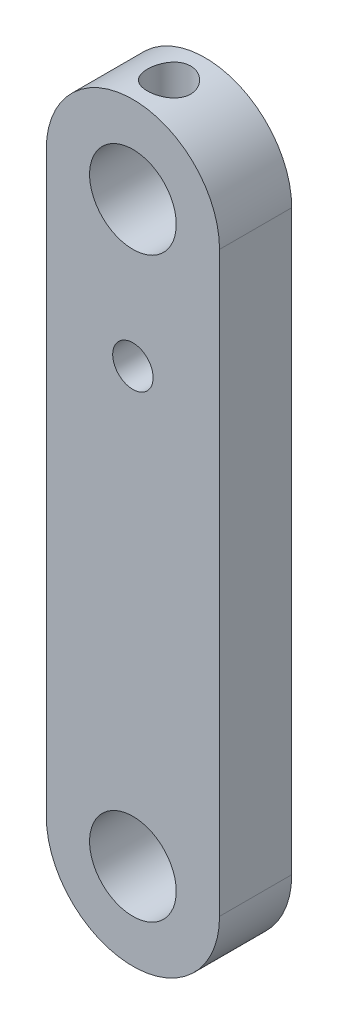
SolidWorks part; units mm, degrees
other "Uwaga1"
sketch "Szkic5" plane through (-6, 6, 0) normal (-0.3769, 0.9094, -0.176) x (0.7575, 0.412, 0.5065)
sketch "Szkic6" plane through (-6, 6, 0) normal (-0.3769, 0.9094, -0.176) x (0.7575, 0.412, 0.5065)
material "Stop 1060"
ref_plane "Płaszczyzna przednia" through (0, 0, 0) normal (0, 0, 1) x (1, 0, 0)
ref_plane "Płaszczyzna górna" through (0, 0, 0) normal (0, 1, 0) x (1, 0, 0)
ref_plane "Płaszczyzna prawa" through (0, 0, 0) normal (1, 0, 0) x (0, 0, -1)
sketch "Szkic1" plane through (0, 0, 0) normal (0, 0, 1) x (1, 0, 0)
  line L0 (0, 0) -> (0, -40)
  line L1 (6, -40) -> (6, 0)
  line L2 (-6, 0) -> (-6, -40)
  arc A1 (6, 0) -> (-6, 0) centre (0, 0) ccw
  circle A2 centre (0, -40) radius 3
  arc A3 (-6, -40) -> (6, -40) centre (0, -40) ccw
  circle A8 centre (0, -10) radius 1.4
  circle A9 centre (0, 0) radius 3
  dimension "D1" = 6
  dimension "D2" = 12
  dimension "D4" = 6
  dimension "D5" = 12
  dimension "D7" = 2.8
  dimension "D8" = 10
  dimension "D3" = 40
extrude "Dodanie-wyciągnięcie1" add sketch "Szkic1" along normal blind 5 contours L2 A3 L1 A1 A2 region at (0, -45.4663, 0)
ref_plane "Płaszczyzna2" through (0, 6, 0) normal (0, 1, 0) x (1, 0, 0)
sketch "Szkic4" plane through (0, 6, 0) normal (0, 1, 0) x (1, 0, 0)
  line L0 (6, -5) -> (6, 0) construction
  line L1 (6, 0) -> (-6, 0) construction
  circle A0 centre (0, -2.5) radius 1.5
  dimension "D1" = 6
  dimension "D2" = 2.5
  dimension "D3" = 3
extrude "Wytnij-wyciągnięcie1" cut sketch "Szkic4" against normal up to next
